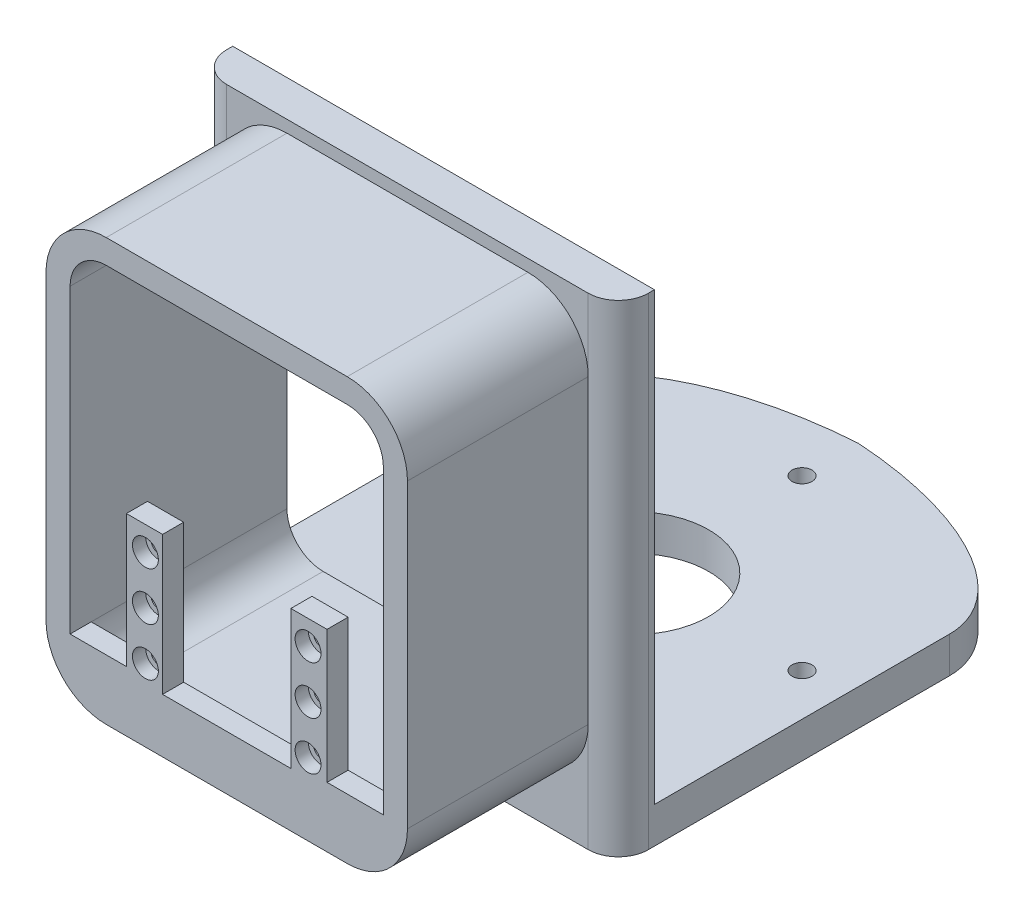
SolidWorks part; units mm, degrees
ref_plane "Front Plane" through (0, 0, 0) normal (0, 0, 1) x (1, 0, 0)
ref_plane "Top Plane" through (0, 0, 0) normal (0, 1, 0) x (1, 0, 0)
ref_plane "Right Plane" through (0, 0, 0) normal (1, 0, 0) x (0, 0, -1)
sketch "Sketch1" plane through (0, 0, 0) normal (0, 0, 1) x (1, 0, 0)
  line L1 (-20, -35) -> (20, -35)
  line L2 (-30, -25) -> (-30, 25)
  line L3 (-20, 35) -> (20, 35)
  line L4 (30, -25) -> (30, 25)
  line L5 (-30, -35) -> (30, 35) construction
  line L6 (-30, 35) -> (30, -35) construction
  arc A1 (20, 35) -> (30, 25) centre (20, 25) cw
  arc A2 (20, -35) -> (30, -25) centre (20, -25) ccw
  arc A3 (-20, -35) -> (-30, -25) centre (-20, -25) cw
  arc A4 (-30, 25) -> (-20, 35) centre (-20, 25) cw
  point P0 (0, 0)
  dimension "D1" = 60
  dimension "D3" = 10
  dimension "D2" = 70
extrude "Boss-Extrude1" add sketch "Sketch1" against normal blind 30
ref_plane "Plane1" through (60, 0, 0) normal (1, 0, 0) x (0, 0, -1)
ref_plane "Plane2" through (60, 0, 0) normal (1, 0, 0) x (0, 0, -1)
sketch "Sketch10" plane through (0, 0, -30) normal (0, 0, -1) x (-1, 0, 0)
  line L0 (0, -3) -> (0, 0) construction
  line L1 (-35, -43) -> (35, -43)
  line L2 (-35, -43) -> (-35, 37)
  line L3 (-35, 37) -> (35, 37)
  line L4 (35, -43) -> (35, 37)
  line L5 (-35, -43) -> (35, 37) construction
  line L6 (-35, 37) -> (35, -43) construction
  point P0 (0, -3)
  dimension "D3" = 3
  dimension "D1" = 80
  dimension "D2" = 70
extrude "Boss-Extrude6" add sketch "Sketch10" along normal blind 75
sketch "Sketch14" plane through (0, 0, 0) normal (0, 0, 1) x (1, 0, 0)
  line L8 (20, 31) -> (-20, 31)
  line L9 (26, -25) -> (26, 25)
  line L10 (-20, -31) -> (20, -31)
  line L11 (-26, 25) -> (-26, -25)
  line L12 (20, 31) -> (-20, 31)
  line L13 (26, -25) -> (26, 25)
  line L14 (-20, -31) -> (20, -31)
  line L15 (-26, 25) -> (-26, -25)
  arc A10 (26, 25) -> (20, 31) centre (20, 25) ccw
  arc A11 (20, -31) -> (26, -25) centre (20, -25) ccw
  arc A12 (-26, -25) -> (-20, -31) centre (-20, -25) ccw
  arc A13 (-20, 31) -> (-26, 25) centre (-20, 25) ccw
  arc A14 (26, 25) -> (20, 31) centre (20, 25) ccw
  arc A15 (20, -31) -> (26, -25) centre (20, -25) ccw
  arc A16 (-26, -25) -> (-20, -31) centre (-20, -25) ccw
  arc A17 (-20, 31) -> (-26, 25) centre (-20, 25) ccw
  dimension "D1" = 4
extrude "Cut-Extrude7" cut sketch "Sketch14" against normal blind 46
sketch "Sketch15" plane through (0, 0, 0) normal (0, 0, 1) x (1, 0, 0)
  line L0 (0, 0) -> (0, -17.9719) construction
  line L1 (-16.65, -3) -> (-10.65, -3)
  line L2 (-10.65, -3) -> (-10.65, -26)
  line L3 (-10.65, -26) -> (10.65, -26)
  line L4 (10.65, -26) -> (10.65, -3)
  line L5 (10.65, -3) -> (16.65, -3)
  line L6 (16.65, -3) -> (16.65, -25)
  line L8 (-16.65, -3) -> (-16.65, -25)
  line L10 (0, 0) -> (13.5, 0) construction
  line L11 (13.5, 0) -> (13.5, -7) construction
  line L12 (13.5, -7) -> (13.5, -15) construction
  line L13 (13.5, -15) -> (13.5, -23) construction
  line L14 (-20, -31) -> (20, -31) construction
  line L15 (-20, -31) -> (20, -31)
  line L16 (26, -25) -> (16.65, -25)
  line L17 (-26, -25) -> (-16.65, -25)
  circle A0 centre (0, 0) radius 11 construction
  circle A1 centre (13.5, -7) radius 1.25
  circle A3 centre (13.5, -15) radius 1.25
  circle A4 centre (13.5, -23) radius 1.25
  circle A5 centre (-13.5, -7) radius 1.25
  circle A6 centre (-13.5, -15) radius 1.25
  circle A7 centre (-13.5, -23) radius 1.25
  arc A9 (-26, -25) -> (-20, -31) centre (-20, -25) ccw
  arc A10 (26, -25) -> (20, -31) centre (20, -25) cw
  point P5 (0, -26)
  dimension "D1" = 22
  dimension "D5" = 2.5
  dimension "D2" = 21.3
  dimension "D3" = 13.5
  dimension "D4" = 7
  dimension "D6" = 8
  dimension "D7" = 8
  dimension "D8" = 6
  dimension "D9" = 5
  dimension "D10" = 3
extrude "Boss-Extrude7" add sketch "Sketch15" against normal blind 3.5
sketch "Sketch17" plane through (0, 0, 0) normal (0, 0, 1) x (1, 0, 0)
  circle A0 centre (-13.5, -7) radius 2.15
  circle A1 centre (-13.5, -15) radius 2.15
  circle A2 centre (-13.5, -23) radius 2.15
  circle A3 centre (13.5, -7) radius 2.15
  circle A4 centre (13.5, -15) radius 2.15
  circle A5 centre (13.5, -23) radius 2.15
  dimension "D1" = 4.3
extrude "Cut-Extrude9" cut sketch "Sketch17" against normal blind 2.2
sketch "Sketch19" plane through (35, 0, 0) normal (1, 0, 0) x (0, 0, -1)
  line L0 (105, -43) -> (30, -43) construction
  line L1 (105, 37) -> (36, 37)
  line L2 (105, 37) -> (105, -37)
  line L3 (105, -37) -> (36, -37)
  line L4 (36, 37) -> (36, -37)
  line L5 (30, 37) -> (30, -43) construction
  dimension "D1" = 6
  dimension "D2" = 6
extrude "Cut-Extrude11" cut sketch "Sketch19" against normal blind 70
sketch "Sketch20" plane through (0, -43, 0) normal (0, -1, 0) x (1, 0, 0)
  line L0 (-35, -30) -> (35, -105) construction
  line L1 (28, -67.5) -> (0, -67.5) construction
  circle A0 centre (28, -67.5) radius 1.65
  circle A1 centre (0, -95.5) radius 1.65
  circle A2 centre (-28, -67.5) radius 1.65
  circle A3 centre (0, -39.5) radius 1.65
  point P6 (0, -67.5)
  point P7 (-9.9827, -95.9761)
  point P9 (0, -67.5)
  point P16 (0, -67.5)
  dimension "D1" = 3.3
  dimension "D3" = 28
  dimension "D2" = 4
extrude "Cut-Extrude12" cut sketch "Sketch20" against normal blind 10
sketch "Sketch21" plane through (0, -37, 0) normal (0, 1, 0) x (1, 0, 0)
  line L0 (-28, 67.5) -> (28, 67.5) construction
  circle A0 centre (0, 67.5) radius 12.5
  dimension "D1" = 25
extrude "Cut-Extrude13" cut sketch "Sketch21" against normal blind 10
fillet "Fillet2" radius 20 2 edges at (35, -40, -105) (-35, -40, -105) second distance 40 first distance on face at (35, -14.3333, -57) first distance on face at (-35, -14.3333, -57)
fillet "Fillet4" radius 5 2 edges at (35, -3, -30) (-35, -3, -30)
